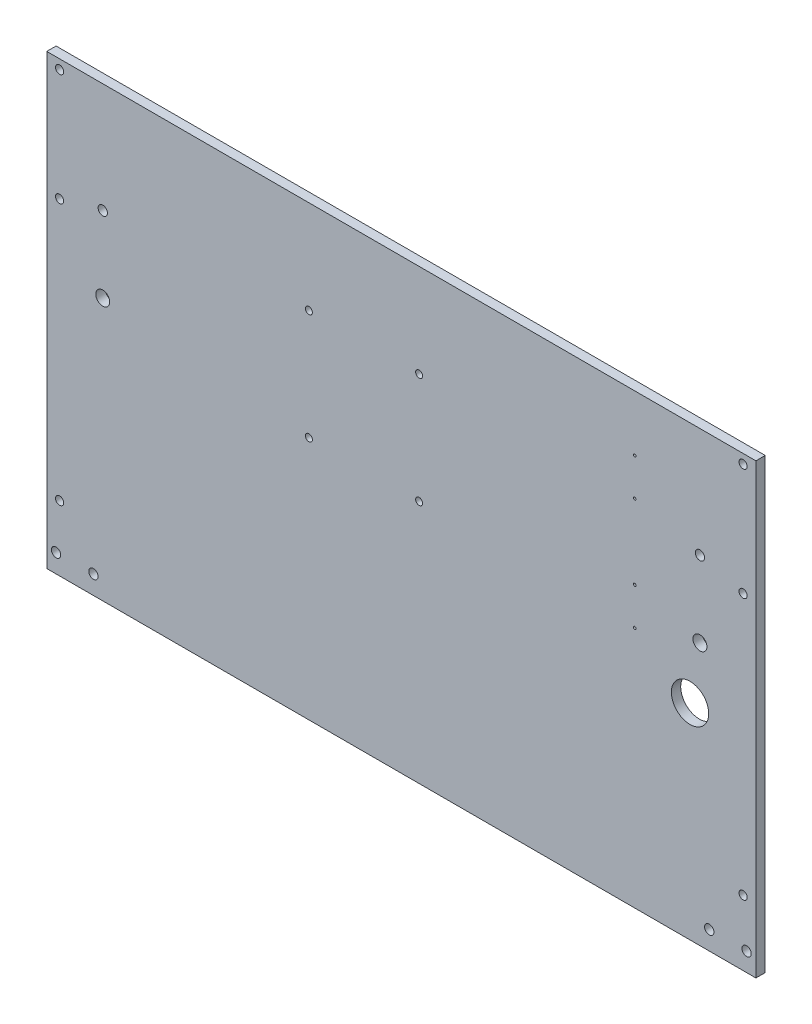
SolidWorks part; units mm, degrees
ref_plane "Front Plane" through (0, 0, 0) normal (0, 0, 1) x (1, 0, 0)
ref_plane "Top Plane" through (0, 0, 0) normal (0, 1, 0) x (1, 0, 0)
ref_plane "Right Plane" through (0, 0, 0) normal (1, 0, 0) x (0, 0, -1)
sketch "Sketch1" plane through (0, 0, 0) normal (0, 0, 1) x (1, 0, 0)
  line L1 (-241.3, -152.4) -> (241.3, -152.4)
  line L2 (-241.3, -152.4) -> (-241.3, 152.4)
  line L3 (-241.3, 152.4) -> (241.3, 152.4)
  line L4 (241.3, -152.4) -> (241.3, 152.4)
  line L5 (-241.3, -152.4) -> (241.3, 152.4) construction
  line L6 (-241.3, 152.4) -> (241.3, -152.4) construction
  point P0 (0, 0)
  dimension "D1" = 482.6
  dimension "D2" = 304.8
extrude "Boss-Extrude1" add sketch "Sketch1" along normal blind 6.35
sketch "Sketch2" plane through (0, 0, 6.35) normal (0, 0, 1) x (1, 0, 0)
  line L0 (-241.3, 0) -> (241.3, 0) construction
  line L1 (-241.3, 152.4) -> (-241.3, -152.4) construction
  line L2 (241.3, -152.4) -> (241.3, 152.4) construction
  line L3 (241.3, 152.4) -> (-241.3, 152.4) construction
  circle A0 centre (-232.5624, 146.05) radius 2.7813
  circle A1 centre (-232.5624, -107.95) radius 2.7813
  circle A2 centre (-232.5624, 69.85) radius 2.7813
  dimension "D2" = 5.5626
  dimension "D3" = 5.5626
  dimension "D6" = 5.5626
  dimension "D1" = 8.7376
  dimension "D4" = 6.35
  dimension "D5" = 254
  dimension "D7" = 76.2
extrude "Cut-Extrude1" cut sketch "Sketch2" against normal through all
mirror "Mirror1" about plane through (0, 0, 0) normal (1, 0, 0) of "Cut-Extrude1"
sketch "Sketch3" plane through (0, 0, 6.35) normal (0, 0, 1) x (1, 0, 0)
  line L0 (-241.3, -139.7) -> (241.3, -139.7) construction
  line L1 (-241.3, 152.4) -> (-241.3, -152.4) construction
  line L2 (241.3, -152.4) -> (241.3, 152.4) construction
  line L3 (-241.3, -152.4) -> (241.3, -152.4) construction
  circle A0 centre (-234.95, -139.7) radius 3.175
  circle A1 centre (-209.55, -139.7) radius 3.175
  dimension "D2" = 6.35
  dimension "D3" = 6.35
  dimension "D4" = 25.4
  dimension "D5" = 6.35
  dimension "D1" = 12.7
extrude "Cut-Extrude2" cut sketch "Sketch3" against normal through all
mirror "Mirror2" about plane through (0, 0, 0) normal (1, 0, 0) of "Cut-Extrude2"
sketch "Sketch4" plane through (0, 0, 6.35) normal (0, 0, 1) x (1, 0, 0)
  line L0 (241.3, 152.4) -> (-241.3, 152.4) construction
  circle A0 centre (196.469, -12.7) radius 12.7
  dimension "D2" = 25.4
  dimension "D1" = 196.469
  dimension "D3" = 165.1
extrude "Cut-Extrude3" cut sketch "Sketch4" against normal through all
sketch "Sketch5" plane through (0, 0, 6.35) normal (0, 0, 1) x (1, 0, 0)
  line L0 (241.3, 152.4) -> (-241.3, 152.4) construction
  line L1 (-62.9, 13.9) -> (12.1, 13.9) construction
  line L2 (-62.9, 13.9) -> (-62.9, 88.9) construction
  line L3 (-62.9, 88.9) -> (12.1, 88.9) construction
  line L4 (12.1, 13.9) -> (12.1, 88.9) construction
  line L5 (-62.9, 13.9) -> (12.1, 88.9) construction
  line L6 (-62.9, 88.9) -> (12.1, 13.9) construction
  circle A0 centre (-62.9, 88.9) radius 2.3749
  circle A1 centre (12.1, 88.9) radius 2.3749
  circle A2 centre (12.1, 13.9) radius 2.3749
  circle A3 centre (-62.9, 13.9) radius 2.3749
  point P0 (-25.4, 51.4)
  dimension "D4" = 4.7498
  dimension "D5" = 4.7498
  dimension "D6" = 4.7498
  dimension "D7" = 4.7498
  dimension "D1" = 75
  dimension "D2" = 75
  dimension "D3" = 63.5
  dimension "D8" = 25.4
extrude "Cut-Extrude4" cut sketch "Sketch5" against normal through all
sketch "Sketch6" plane through (0, 0, 6.35) normal (0, 0, 1) x (1, 0, 0)
  line L0 (241.3, -152.4) -> (241.3, 152.4) construction
  line L1 (-241.3, 152.4) -> (-241.3, -152.4) construction
  circle A0 centre (-203.2, 77.7271) radius 3.175
  circle A1 centre (-203.2, 26.0961) radius 4.7625
  circle A2 centre (203.2, 77.7271) radius 3.175
  circle A3 centre (203.2, 26.0961) radius 4.7625
  dimension "D1" = 6.35
  dimension "D2" = 6.35
  dimension "D3" = 9.525
  dimension "D4" = 9.525
  dimension "D5" = 38.1
  dimension "D6" = 38.1
extrude "Cut-Extrude5" cut sketch "Sketch6" against normal through all
sketch "Sketch7" plane through (0, 0, 6.35) normal (0, 0, 1) x (1, 0, 0)
  line L0 (158.8215, 152.4) -> (158.8215, -152.4) construction
  line L1 (241.3, 152.4) -> (-241.3, 152.4) construction
  line L2 (-241.3, -152.4) -> (241.3, -152.4) construction
  circle A0 centre (158.8215, 114.3) radius 0.889
  circle A1 centre (158.8215, 88.9) radius 0.889
  circle A2 centre (158.8215, 38.1) radius 0.889
  circle A3 centre (158.8215, 12.7) radius 0.889
  dimension "D1" = 1.778
  dimension "D2" = 1.778
  dimension "D3" = 1.778
  dimension "D4" = 1.778
  dimension "D8" = 38.1
  dimension "D5" = 25.4
  dimension "D6" = 25.4
  dimension "D7" = 50.8
extrude "Cut-Extrude6" cut sketch "Sketch7" against normal through all
